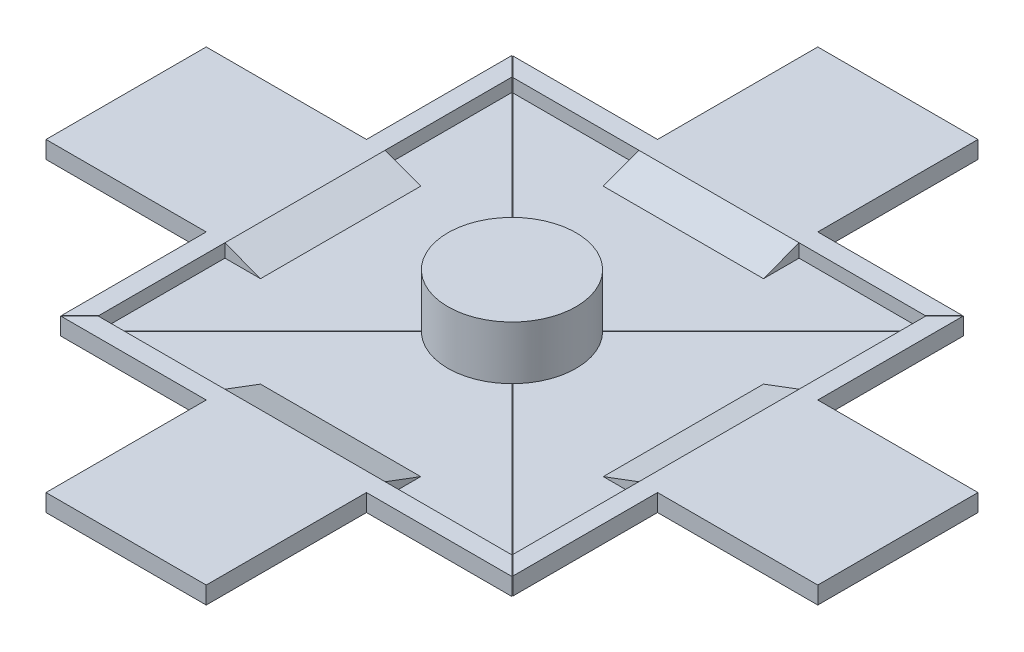
SolidWorks part; units mm, degrees
ref_plane "Front Plane" through (0, 0, 0) normal (0, 0, 1) x (1, 0, 0)
ref_plane "Top Plane" through (0, 0, 0) normal (0, 1, 0) x (1, 0, 0)
ref_plane "Right Plane" through (0, 0, 0) normal (1, 0, 0) x (0, 0, -1)
sketch "Field Layout" plane through (0, 0, 0) normal (0, 1, 0) x (1, 0, 0)
  line L0 (-984.25, -984.25) -> (984.25, -984.25)
  line L1 (-984.25, -984.25) -> (-984.25, 984.25)
  line L2 (-984.25, 984.25) -> (984.25, 984.25)
  line L3 (984.25, 984.25) -> (984.25, -984.25)
  line L4 (-984.25, -984.25) -> (984.25, 984.25) construction
  line L5 (984.25, -984.25) -> (0, 0)
  line L6 (-984.25, -984.25) -> (0, 0)
  line L7 (0, 0) -> (0, -1950.025) construction
  line L8 (-1073.15, 1073.15) -> (1073.15, 1073.15)
  line L9 (-1073.15, 1073.15) -> (-1073.15, -1073.15)
  line L10 (-1073.15, -1073.15) -> (1073.15, -1073.15)
  line L11 (1073.15, 1073.15) -> (1073.15, -1073.15)
  line L12 (-381, -1073.15) -> (381, -1073.15)
  line L13 (-381, -1073.15) -> (-381, -1835.15)
  line L14 (-381, -1835.15) -> (381, -1835.15)
  line L15 (381, -1073.15) -> (381, -1835.15)
  line L16 (-1073.15, 381) -> (-1835.15, 381)
  line L17 (-1073.15, 381) -> (-1073.15, -381)
  line L18 (-1073.15, -381) -> (-1835.15, -381)
  line L19 (-1835.15, 381) -> (-1835.15, -381)
  line L20 (381, 1073.15) -> (381, 1835.15)
  line L21 (381, 1073.15) -> (-381, 1073.15)
  line L22 (-381, 1073.15) -> (-381, 1835.15)
  line L23 (381, 1835.15) -> (-381, 1835.15)
  line L24 (1073.15, -381) -> (1835.15, -381)
  line L25 (1073.15, -381) -> (1073.15, 381)
  line L26 (1073.15, 381) -> (1835.15, 381)
  line L27 (1835.15, -381) -> (1835.15, 381)
  line L28 (381, -1835.15) -> (-381, -1073.15) construction
  line L29 (-152.4, -1746.25) -> (152.4, -1162.05) construction
  line L30 (-152.4, -1746.25) -> (152.4, -1746.25)
  line L31 (-152.4, -1746.25) -> (-152.4, -1162.05)
  line L32 (-152.4, -1162.05) -> (152.4, -1162.05)
  line L33 (152.4, -1746.25) -> (152.4, -1162.05)
  line L34 (-984.25, 381) -> (-815.1118, 381)
  line L35 (-381, -984.25) -> (381, -984.25)
  line L36 (-381, -984.25) -> (-381, -815.1118)
  line L37 (-381, -815.1118) -> (381, -815.1118)
  line L38 (381, -984.25) -> (381, -815.1118)
  line L39 (-815.1118, 381) -> (-815.1118, -381)
  line L40 (-984.25, -381) -> (-815.1118, -381)
  line L41 (-1746.25, 152.4) -> (-1162.05, 152.4)
  line L42 (-1746.25, 152.4) -> (-1746.25, -152.4)
  line L43 (-1746.25, -152.4) -> (-1162.05, -152.4)
  line L44 (-1162.05, 152.4) -> (-1162.05, -152.4)
  line L45 (381, 984.25) -> (381, 815.1118)
  line L46 (381, 815.1118) -> (-381, 815.1118)
  line L47 (-381, 984.25) -> (-381, 815.1118)
  line L48 (152.4, 1746.25) -> (152.4, 1162.05)
  line L49 (152.4, 1746.25) -> (-152.4, 1746.25)
  line L50 (-152.4, 1746.25) -> (-152.4, 1162.05)
  line L51 (152.4, 1162.05) -> (-152.4, 1162.05)
  line L52 (984.25, -381) -> (815.1118, -381)
  line L53 (815.1118, -381) -> (815.1118, 381)
  line L54 (984.25, 381) -> (815.1118, 381)
  line L55 (1746.25, -152.4) -> (1162.05, -152.4)
  line L56 (1746.25, -152.4) -> (1746.25, 152.4)
  line L57 (1746.25, 152.4) -> (1162.05, 152.4)
  line L58 (1162.05, -152.4) -> (1162.05, 152.4)
  circle A0 centre (0, 0) radius 304.8
  point P2 (0, 0)
  point P16 (0, -1454.15)
  point P32 (0, 0)
  point P66 (0, 0)
  dimension "D3" = 609.6
  dimension "D1" = 1968.5
  dimension "D2" = 1968.5
  dimension "D4" = 88.9
  dimension "D5" = 88.9
  dimension "D6" = 762
  dimension "D8" = 584.2
  dimension "D9" = 304.8
  dimension "D7" = 4
  dimension "D10" = 4
extrude "Plywood Base" add sketch "Field Layout" against normal blind 19.05 contours L16 L19 L18 L9 L41 L44 L43 L42 | L44 L41 L42 L43 | L11 L8 L9 L10 L2 L3 L0 L1 | L1 L40 L39 L34 | A0 L5 L3 L52 L53 L54 L2 L45 L46 L47 L1 L34 L39 L40 L6 | A0 L6 L0 L36 L37 L38 L5 | L6 A0 L5 | L5 A0 L6 | L0 L38 L37 L36 | L30 L33 L32 L31 | L15 L10 L13 L14 L33 L30 L31 L32 | L3 L54 L53 L52 | L24 L27 L26 L11 L55 L58 L57 L56 | L58 L55 L56 L57 | L2 L47 L46 L45 | L20 L23 L22 L8 L48 L51 L50 L49 | L51 L48 L49 L50 region at (0, 0, 660.2665) region at (-956.4112, 0, 682.625) region at (0, 0, 899.6809) region at (-899.6809, 0, 0) region at (0, 0, -60.9814) region at (0, 0, 182.9443) region at (899.6809, 0, 0) region at (0, 0, -899.6809) region at (-727.075, 0, -1042.7967) region at (-370.2237, 0, -1454.15) region at (-1083.9263, 0, 0) region at (1454.15, 0, -370.2237) region at (0, 0, 1083.9263) region at (0, 0, 1454.15) region at (-1454.15, 0, 0) region at (0, 0, -1454.15) region at (1454.15, 0, 0)
extrude "Raised Base" add sketch "Field Layout<3>" along normal blind 63.5 contours L16 L19 L18 L9 L41 L44 L43 L42 | L44 L41 L42 L43 | L11 L8 L9 L10 L2 L3 L0 L1 | L15 L10 L13 L14 L33 L30 L31 L32 | L30 L33 L32 L31 | L58 L55 L56 L57 | L24 L27 L26 L11 L55 L58 L57 L56 | L51 L48 L49 L50 | L20 L23 L22 L8 L48 L51 L50 L49 region at (-727.075, 0, -1042.7967) region at (-370.2237, 0, -1454.15) region at (-1083.9263, 0, 0) region at (1454.15, 0, -370.2237) region at (0, 0, 1083.9263) region at (0, 0, 1454.15) region at (-1454.15, 0, 0) region at (0, 0, -1454.15) region at (1454.15, 0, 0)
sketch "Field Layout<3>" plane through (0, 0, 0) normal (0, 1, 0) x (1, 0, 0) same geometry as "Field Layout"
extrude "Ramp Extrude" add sketch "Field Layout<4>" along normal blind 63.5 contours L0 L38 L37 L36 region at (0, 0, 899.6809)
sketch "Field Layout<4>" plane through (0, 0, 0) normal (0, 1, 0) x (1, 0, 0) same geometry as "Field Layout"
sketch "Sketch3" plane through (381, 0, 0) normal (1, 0, 0) x (0, 0, -1)
  line L4 (-984.25, 63.5) -> (-815.1118, 0)
  line L8 (-984.25, 0) -> (-815.1118, 0)
  line L9 (-815.1118, 0) -> (-815.1118, 63.5)
  line L10 (-815.1118, 63.5) -> (-984.25, 63.5)
  line L11 (-984.25, 63.5) -> (-984.25, 0)
  line L12 (-984.25, 0) -> (-815.1118, 0)
  line L13 (-815.1118, 0) -> (-815.1118, 63.5)
  line L14 (-815.1118, 63.5) -> (-984.25, 63.5)
  line L15 (-984.25, 63.5) -> (-984.25, 0)
  line M6 (-815.1118, 0) -> (-815.1118, 63.5)
  line M7 (-815.1118, 63.5) -> (-984.25, 63.5)
  dimension "D1" = 0
extrude "Cut ramp slope" cut sketch "Sketch3" against normal up to next contours L4 M7 M6 region at (381, 42.3333, 871.4912)
pattern_circular "Copy Ramp Slope" count 4 over 360 about axis through (0, -19.05, 0) along (0, -1, 0) of "Ramp Extrude", "Cut ramp slope"
sketch "Sketch5" plane through (0, 0, 0) normal (0, 1, 0) x (1, 0, 0)
  circle A0 centre (0, 0) radius 304.8
  dimension "D1" = 609.6
extrude "Boss-Extrude1" add sketch "Sketch5" along normal blind 254 separate body
sketch "Sketch4" plane through (0, 0, 0) normal (0, 1, 0) x (1, 0, 0)
  line L0 (-984.25, -984.25) -> (984.25, 984.25)
  line L1 (-984.25, 984.25) -> (984.25, -984.25)
  line L3 (984.25, 984.25) -> (1073.15, 1073.15)
  line L4 (-984.25, -984.25) -> (-1073.15, -1073.15)
  line L5 (984.25, -984.25) -> (1073.15, -1073.15)
  line L6 (-984.25, 984.25) -> (-1073.15, 1073.15)
extrude "Cut-Extrude-Thin1" cut sketch "Sketch4" against normal through all both and the other way through all thin thin type one direction wall 2.54
